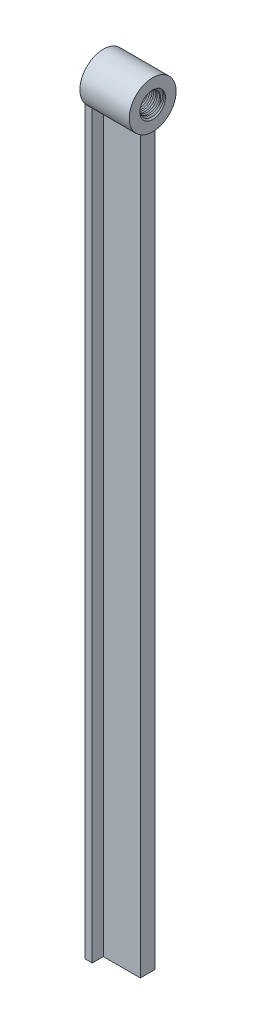
SolidWorks part; units mm, degrees
ref_plane "Front Plane" through (0, 0, 0) normal (0, 0, 1) x (1, 0, 0)
ref_plane "Top Plane" through (0, 0, 0) normal (0, 1, 0) x (1, 0, 0)
ref_plane "Right Plane" through (0, 0, 0) normal (1, 0, 0) x (0, 0, -1)
sketch "Sketch1" plane through (0, 0, 0) normal (0, 0, 1) x (1, 0, 0)
  line L0 (0, 0) -> (101.5385, 0) construction
  line L1 (0, -6) -> (0, -306)
  line L2 (0, -306) -> (-15, -306)
  line L3 (-15, -306) -> (-15, -6)
  line L4 (-15, -6) -> (0, -6)
  dimension "D1" = 15
  dimension "D2" = 6
  dimension "D3" = 300
extrude "Boss-Extrude1" add sketch "Sketch1" along normal mid plane 6
sketch "Sketch5" plane through (0, 0, 0) normal (0, 0, 1) x (1, 0, 0)
  line L1 (-18, -6) -> (-15, -6)
  line L2 (-18, -6) -> (-18, -306)
  line L3 (-18, -6) -> (-18, -306) construction
  line L4 (-18, -306) -> (-15, -306)
  line L5 (-18, -6) -> (-18, -306)
  line L6 (-15, -6) -> (-15, -306)
  dimension "D1" = 3
extrude "Boss-Extrude2" add sketch "Sketch5" along normal mid plane 15
sketch "Sketch7" plane through (0, 0, 0) normal (1, 0, 0) x (0, 0, -1)
  line L0 (0, 0) -> (0, -6) construction
  line L1 (-3, -6) -> (3, -6) construction
  circle A0 centre (0, 0) radius 9.5
  dimension "D2" = 19
  dimension "D1" = 6
extrude "Boss-Extrude3" add sketch "Sketch7" along normal blind 2 and the other way blind 18
sketch "Sketch8" plane through (2, 0, 0) normal (1, 0, 0) x (0, 0, -1)
  circle A0 centre (0, 0) radius 4.19
  dimension "D1" = 8.38
extrude "Cut-Extrude1" cut sketch "Sketch8" against normal up to next
chamfer "Chamfer1" distance 1 angle 45 2 edges at (-18, 4.19, 0) (2, 4.19, 0)
sketch "Sketch9" plane through (2, 0, 0) normal (1, 0, 0) x (0, 0, -1)
  circle A0 centre (0, 0) radius 4.19 construction
  circle A1 centre (0, 0) radius 4.19
curve "Helix/Spiral1" pitch 1.5 height 22.5 radius 4.19 centre (2, 0, 0) axis (-1, 0, 0) start towards (0, 0, 1)
sketch "Sketch10" plane through (0, 0, 0) normal (0, 0, 1) x (1, 0, 0)
  line L0 (2, -9.5) -> (2, 9.5) construction
  line L1 (2, 4.99) -> (1.3072, 3.79)
  line L2 (1.3072, 3.79) -> (2.6928, 3.79)
  line L3 (2.6928, 3.79) -> (2, 4.99)
  circle A0 centre (2, 4.19) radius 0.4 construction
  dimension "D1" = 1.2
  dimension "D2" = 0.2
  dimension "D3" = 60
sweep "Cut-Sweep1" cut profiles "Sketch10" path "Helix/Spiral1" align with end faces yes
